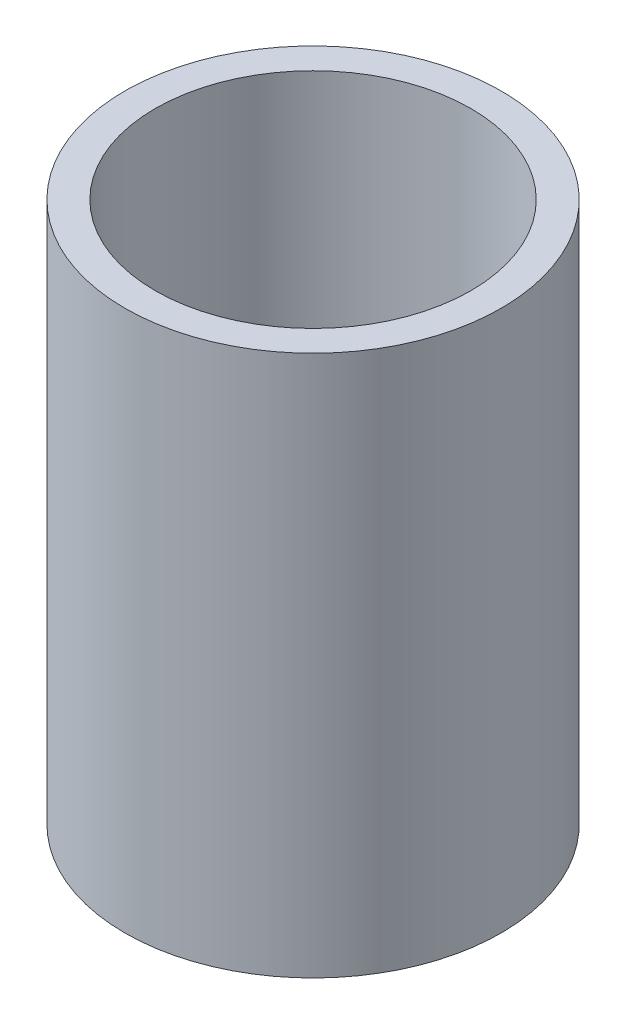
SolidWorks part; units mm, degrees
ref_plane "Front Plane" through (0, 0, 0) normal (0, 0, 1) x (1, 0, 0)
ref_plane "Top Plane" through (0, 0, 0) normal (0, 1, 0) x (1, 0, 0)
ref_plane "Right Plane" through (0, 0, 0) normal (1, 0, 0) x (0, 0, -1)
sketch "Sketch1" plane through (0, 0, 0) normal (0, 1, 0) x (1, 0, 0)
  circle A0 centre (0, 0) radius 17.5
  dimension "SLEEVE_OD" = 35
extrude "Boss-Extrude1" add sketch "Sketch1" along normal blind 50.3109
sketch "Sketch2" plane through (0, 0, 0) normal (0, 1, 0) x (1, 0, 0)
  circle A0 centre (0, 0) radius 14.6761
  dimension "BORE_D" = 29.3522
extrude "Cut-Extrude1" cut sketch "Sketch2" along normal through all
chamfer "Chamfer1" distance 2.4193 angle 34.031 rebuild error yes
